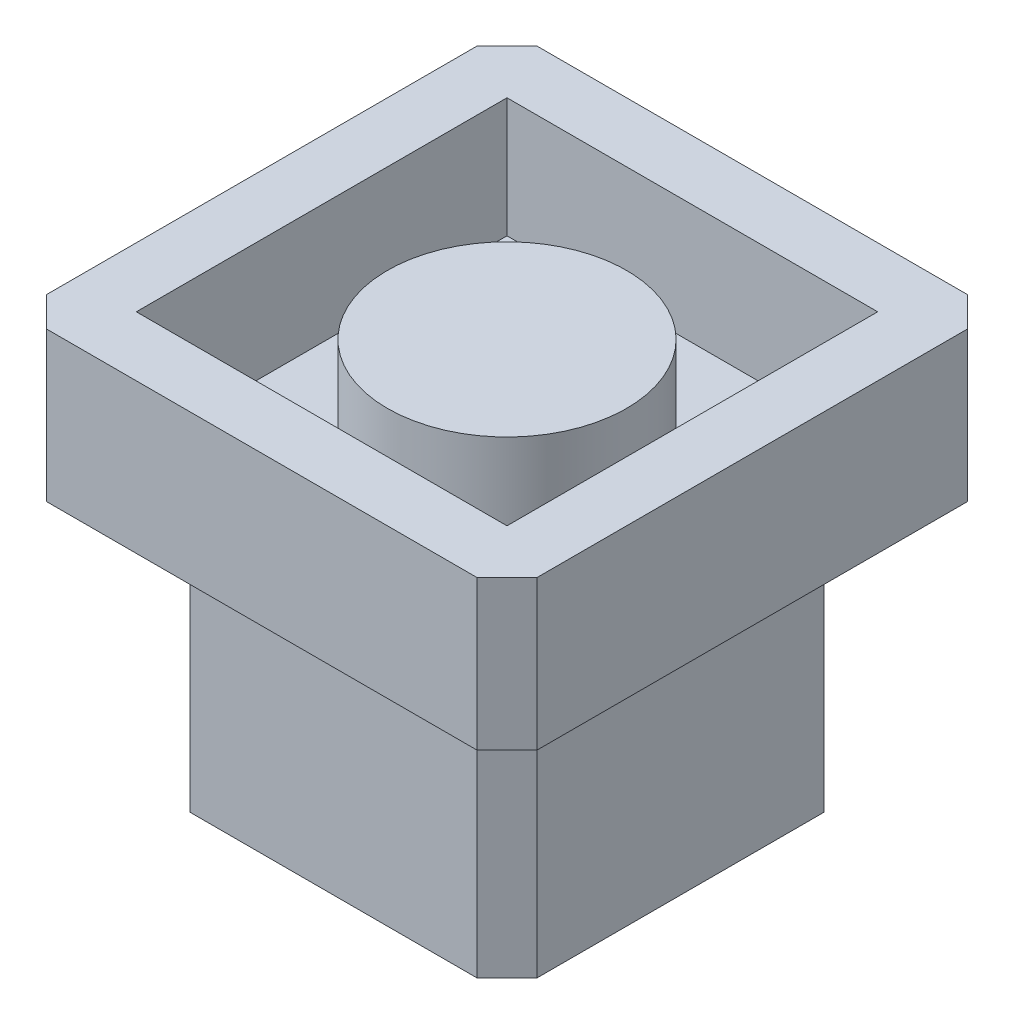
SolidWorks part; units mm, degrees
ref_plane "Front Plane" through (0, 0, 0) normal (0, 0, 1) x (1, 0, 0)
ref_plane "Top Plane" through (0, 0, 0) normal (0, 1, 0) x (1, 0, 0)
ref_plane "Right Plane" through (0, 0, 0) normal (1, 0, 0) x (0, 0, -1)
sketch "Sketch1" plane through (0, 0, 0) normal (0, 1, 0) x (1, 0, 0)
  line L0 (-4.1, 4.1) -> (-4.1, -4.1)
  line L1 (-3.1, 3.1) -> (3.1, 3.1)
  line L2 (-3.1, 3.1) -> (-3.1, -3.1)
  line L3 (-3.1, -3.1) -> (3.1, -3.1)
  line L4 (3.1, 3.1) -> (3.1, -3.1)
  line L5 (-3.1, 3.1) -> (3.1, -3.1) construction
  line L6 (-3.1, -3.1) -> (3.1, 3.1) construction
  line L7 (-4.1, -4.1) -> (4.1, -4.1)
  line L8 (4.1, 4.1) -> (4.1, -4.1)
  line L9 (-4.1, 4.1) -> (4.1, 4.1)
  circle A1 centre (0, 0) radius 2
  dimension "D1" = 4
  dimension "D2" = 6.2
  dimension "D3" = 1
extrude "Boss-Extrude1" add sketch "Sketch1" along normal blind 1.6 contours A1 region at (0, 0, 0)
extrude "Boss-Extrude2" add sketch "Sketch1<3>" along normal blind 2 separate body contours L9 L0 L7 L8 L1 L4 L3 L2 region at (0, 0, -3.984)
sketch "Sketch1<3>" plane through (0, 0, 0) normal (0, 1, 0) x (1, 0, 0) same geometry as "Sketch1"
extrude "Boss-Extrude3" add sketch "Sketch1<4>" against normal blind 0.5 contours L9 L0 L7 L8 L1 L4 L3 L2 | L4 L1 L2 L3 A1 | A1 region at (0, 0, -3.984) region at (0, 0, -3.0123) region at (0, 0, 0)
sketch "Sketch1<4>" plane through (0, 0, 0) normal (0, 1, 0) x (1, 0, 0) same geometry as "Sketch1"
sketch "Sketch3" plane through (0, -0.5, 0) normal (0, -1, 0) x (1, 0, 0)
  line L1 (-2.9, 2.9) -> (2.9, 2.9)
  line L2 (-2.9, 2.9) -> (-2.9, -2.9)
  line L3 (-2.9, -2.9) -> (2.9, -2.9)
  line L4 (2.9, 2.9) -> (2.9, -2.9)
  line L5 (-2.9, 2.9) -> (2.9, -2.9) construction
  line L6 (-2.9, -2.9) -> (2.9, 2.9) construction
  point P0 (0, 0)
  dimension "D1" = 5.8
  dimension "D2" = 5.8
extrude "Boss-Extrude4" add sketch "Sketch3" along normal blind 4.5
chamfer "Chamfer1" distance 0.5 angle 45 8 edges at (-4.1, 0.75, -4.1) (4.1, 0.75, -4.1) (-4.1, 0.75, 4.1) (4.1, 0.75, 4.1) (-2.9, -2.75, 2.9) (2.9, -2.75, 2.9) (-2.9, -2.75, -2.9) (2.9, -2.75, -2.9)
sketch "Sketch4" plane through (0, -5, 0) normal (0, -1, 0) x (1, 0, 0)
  text T0 "A"
extrude "Cut-Extrude1" cut sketch "Sketch4" against normal blind 0.2
